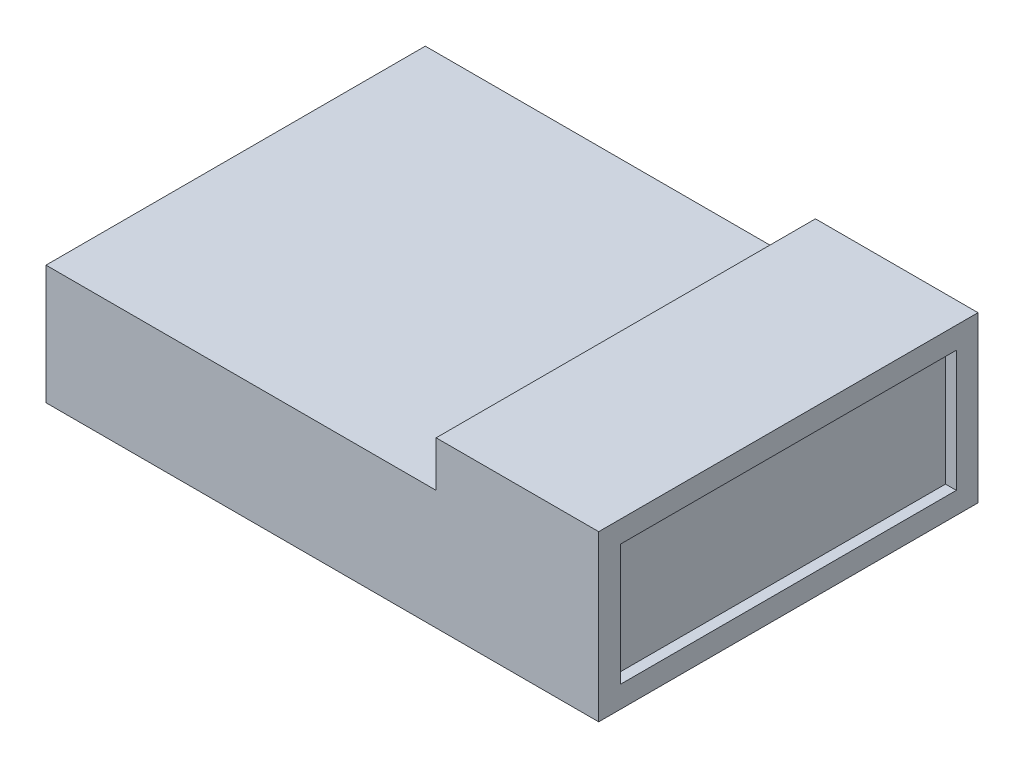
SolidWorks part; units mm, degrees
ref_plane "Front Plane" through (0, 0, 0) normal (0, 0, 1) x (1, 0, 0)
ref_plane "Top Plane" through (0, 0, 0) normal (0, 1, 0) x (1, 0, 0)
ref_plane "Right Plane" through (0, 0, 0) normal (1, 0, 0) x (0, 0, -1)
sketch "Sketch1" plane through (0, 0, 0) normal (0, 1, 0) x (1, 0, 0)
  line L1 (-25.5, 17.5) -> (25.5, 17.5)
  line L2 (-25.5, 17.5) -> (-25.5, -17.5)
  line L3 (-25.5, -17.5) -> (25.5, -17.5)
  line L4 (25.5, 17.5) -> (25.5, -17.5)
  line L5 (25.5, 17.5) -> (10.5, 17.5)
  line L6 (25.5, 17.5) -> (25.5, -17.5)
  line L7 (25.5, -17.5) -> (10.5, -17.5)
  line L8 (10.5, 17.5) -> (10.5, -17.5)
  point P4 (0, 17.5)
  point P6 (-25.5, 0)
  dimension "D1" = 35
  dimension "D2" = 51
  dimension "D3" = 15
extrude "Boss-Extrude1" add sketch "Sketch1" along normal blind 11 contours L8 L1 L2 L3 region at (-7.5, 0, 0)
extrude "Boss-Extrude2" add sketch "Sketch1<3>" along normal blind 15.2 contours L1 L8 L3 L4 region at (18, 0, 0)
sketch "Sketch1<3>" plane through (0, 0, 0) normal (0, 1, 0) x (1, 0, 0) same geometry as "Sketch1"
sketch "Sketch2" plane through (25.5, 0, 0) normal (1, 0, 0) x (0, 0, -1)
  line L0 (-17.5, 15.2) -> (-17.5, 0) construction
  line L1 (-15.5, 13.2) -> (15.5, 13.2)
  line L2 (-15.5, 13.2) -> (-15.5, 2)
  line L3 (-15.5, 2) -> (15.5, 2)
  line L4 (15.5, 13.2) -> (15.5, 2)
  line L5 (17.5, 15.2) -> (17.5, 0) construction
  line L6 (17.5, 15.2) -> (-17.5, 15.2) construction
  line L7 (17.5, 0) -> (-17.5, 0) construction
  dimension "D1" = 2
  dimension "D2" = 2
  dimension "D3" = 2
  dimension "D4" = 2
extrude "Cut-Extrude1" cut sketch "Sketch2" against normal blind 1
